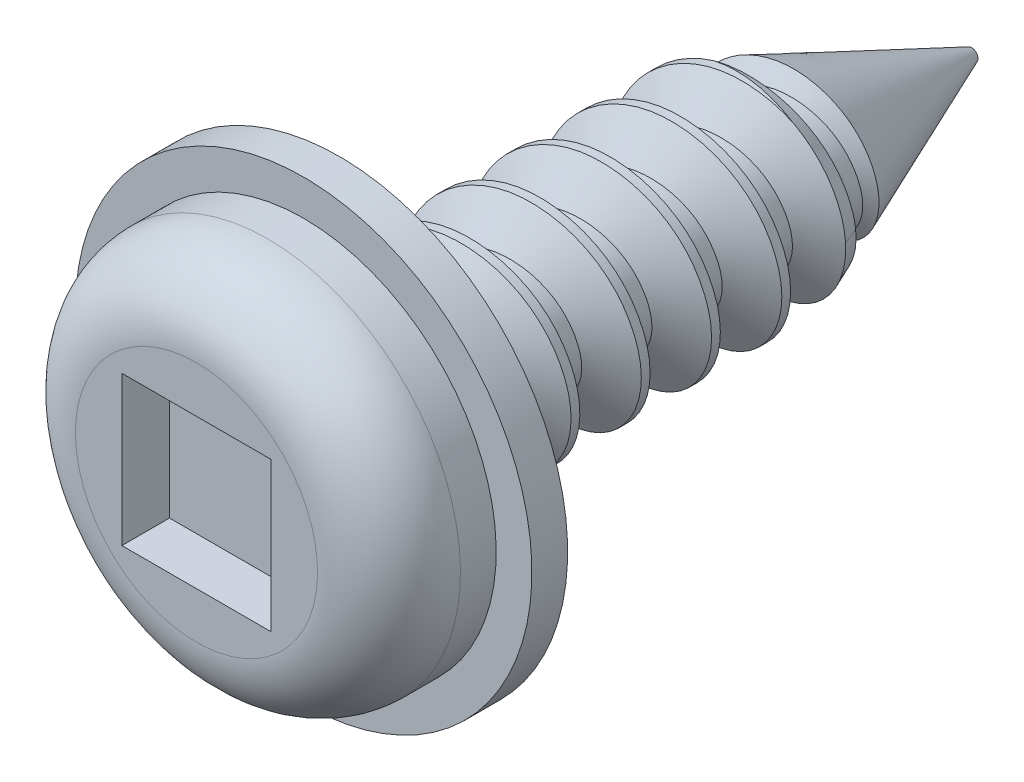
SolidWorks part; units mm, degrees
ref_plane "Front" through (0, 0, 0) normal (0, 0, 1) x (1, 0, 0)
ref_plane "Top" through (0, 0, 0) normal (0, 1, 0) x (1, 0, 0)
ref_plane "Right" through (0, 0, 0) normal (1, 0, 0) x (0, 0, -1)
sketch "Sketch1" plane through (0, 0, 0) normal (0, 0, 1) x (1, 0, 0)
  circle A0 centre (0, 0) radius 4.5847
  dimension "Head Dia" = 9.1694
extrude "Extrude3" add sketch "Sketch1" along normal blind 2.8702
ref_plane "Plane1" through (0, 0, 2.8702) normal (0, 0, 1) x (1, 0, 0)
sketch "Sketch11" plane through (0, 0, 0) normal (1, 0, 0) x (0, 0, -1)
  line L1 (-2.8702, 4.5847) -> (-2.8702, -4.5847) construction
  line L3 (0, 4.5847) -> (-2.8702, 4.5847) construction
  line L4 (-0.7175, 3.8672) -> (-0.7175, 4.5847)
  line L5 (-0.7175, 4.5847) -> (-3.5878, 4.5847)
  line L6 (-3.5878, 4.5847) -> (-3.5878, 0)
  line L7 (-3.5878, 0) -> (-2.8702, 0)
  line L8 (-0.7175, 3.8672) -> (-1.4351, 3.8672)
  line L10 (-2.8702, 0) -> (-2.8702, 2.432)
  line L11 (0, 0) -> (-2.8702, 0) construction
  line L12 (-0.7175, 3.8672) -> (0, 3.8672) construction
  line L13 (0, -4.5847) -> (0, 4.5847) construction
  arc A0 (-1.4351, 3.8672) -> (-2.8702, 2.432) centre (-1.4351, 2.432) ccw
  dimension "D2" = 0.7175
revolve "Cut-Revolve3" cut sketch "Sketch11" angle 360 about L11
sketch "Sketch14" plane through (0, 0, 0) normal (1, 0, 0) x (0, 0, -1)
  line L0 (0.3528, 1.319) -> (0.7938, 2.0828) construction
  line L2 (0.7938, 2.0828) -> (0.9701, 2.0828)
  line L3 (0.9701, 2.0828) -> (1.4111, 1.319) construction
  line L4 (1.4111, 1.319) -> (0.3528, 1.319) construction
  line L5 (1.4111, 1.319) -> (1.7639, 1.319) construction
  line L6 (0.3528, 1.319) -> (0, 1.319) construction
  line L10 (0, 4.5847) -> (0, -4.5847) construction
  line L11 (0.7938, 2.0828) -> (0.3528, 1.319)
  line L12 (0.3528, 1.319) -> (1.4111, 1.319)
  line L13 (1.4111, 1.319) -> (0.9701, 2.0828)
  line L14 (0, 0) -> (-2.8702, 0) construction
  line L15 (0, 0) -> (-2.8702, 0) construction
  point P11 (0.8819, 2.0828)
  dimension "D1" = 60
  dimension "Pitch" = 1.4111
  dimension "D3" = 0.3528
  dimension "D4" = 0.1764
  dimension "Screw Dia" = 4.1656
ref_plane "Plane2" through (0, 0, -0.8819) normal (0, 0, 1) x (1, 0, 0)
sketch "Sketch15" plane through (0, 0, -0.8819) normal (0, 0, 1) x (1, 0, 0)
  circle A0 centre (0, 0) radius 2.0828
curve "Helix/Spiral1" pitch 1.4111 height 2.1167 radius 2.0828 centre (0, 0, -0.8819) axis (0, 0, -1) start towards (0, 1, 0)
sketch "Sketch18" plane through (0, 0, 0) normal (1, 0, 0) x (0, 0, -1)
  line L1 (0, 0) -> (12.7, 0)
  line L2 (0, 0) -> (0, 1.319)
  line L3 (0, 1.319) -> (12.7, 1.319)
  line L4 (12.7, 0) -> (12.7, 1.319)
  dimension "Body Length" = 12.7
revolve "Revolve1" add sketch "Sketch18" angle 360 about L11
sweep "Sweep1" add profiles "Sketch14" path "Helix/Spiral1"
pattern_linear "LPattern3" count 8 spacing 1.4111 along (0, 0, -1) count 2 spacing 1.4111 along (0, 0, 1) of "Sweep1"
sketch "Sketch13" plane through (0, 0, 0) normal (1, 0, 0) x (0, 0, -1)
  line L0 (12.7, 0.127) -> (7.9783, 2.0828)
  line L2 (7.9783, 2.0828) -> (12.7, 2.0828)
  line L3 (12.7, 2.0828) -> (12.7, 0.127) construction
  line L4 (12.7, 0.127) -> (17.78, 0.127)
  line L5 (0, 0) -> (12.7, 0) construction
  line L6 (0.7938, 2.0828) -> (0.9701, 2.0828) construction
  line L7 (17.78, 0.127) -> (17.78, 2.0828)
  line L8 (17.78, 2.0828) -> (12.7, 2.0828)
  dimension "D1" = 0.127
  dimension "D2" = 22.5
  dimension "D3" = 5.08
revolve "Cut-Revolve4" cut sketch "Sketch13" angle 360 about L5
sketch "Sketch12" plane through (0, 0, 2.8702) normal (0, 0, 1) x (1, 0, 0)
  line L0 (-1.4986, -1.4986) -> (1.4986, 1.4986) construction
  line L1 (-1.4986, 1.4986) -> (1.4986, 1.4986)
  line L2 (-1.4986, 1.4986) -> (-1.4986, -1.4986)
  line L3 (-1.4986, -1.4986) -> (1.4986, -1.4986)
  line L4 (1.4986, 1.4986) -> (1.4986, -1.4986)
  dimension "Square" = 2.9972
extrude "Cut-Extrude1" cut sketch "Sketch12" against normal blind 0.9567
sketch "Sketch21" plane through (0, 0, 0) normal (1, 0, 0) x (0, 0, -1)
  line L0 (7.9783, 1.4856) -> (0, 1.4856)
  line L1 (0, 4.5847) -> (0, -4.5847) construction
  line L2 (0, 1.4856) -> (0, 0)
  line L3 (0, 0) -> (12.7, 0)
  line L4 (12.7, 0) -> (10.162, 1.0513)
  line L5 (12.7, 0.127) -> (7.9783, 2.0828) construction
  line L6 (0.3528, 1.319) -> (0, 1.319) construction
  arc A0 (7.9783, 1.4856) -> (10.162, 1.0513) centre (7.9783, -4.2208) cw
  dimension "D1" = 0.1666
revolve "Revolve2" [suppressed] add sketch "Sketch21" angle 360 about L11
sketch "Sketch23" plane through (0, 0, 0) normal (1, 0, 0) x (0, 0, -1)
  line L0 (12.7, 2.0828) -> (12.7, -2.0828) construction
  point P0 (-2.8702, 2.432)
  point P1 (0, 4.5847)
  point P2 (6.985, -2.0828)
  dimension "D1" = 5.715
equation "\"D3@LPattern3\"=\"Pitch@Sketch14\""
equation "\"D1@LPattern3\"=(\"Body Length@Sketch18\"/\"Pitch@Sketch14\")-1"
equation "\"D3@Sketch14\" = \"Pitch@Sketch14\"/4"
equation "\"D4@Sketch14\" = \"Pitch@Sketch14\"/8"
equation "\"D4@LPattern3\" = \"D3@LPattern3\""
equation "\"D4@Helix/Spiral1\" = \"Pitch@Sketch14\""
equation "\"D1@Cut-Extrude1\" = \"Head Ht@Extrude3\"/3"
equation "\"D1@Sketch21\" = \"Screw Dia@Sketch14\"*.04"
equation "\"D2@Sketch11\" = \"Head Ht@Extrude3\"*.25"
